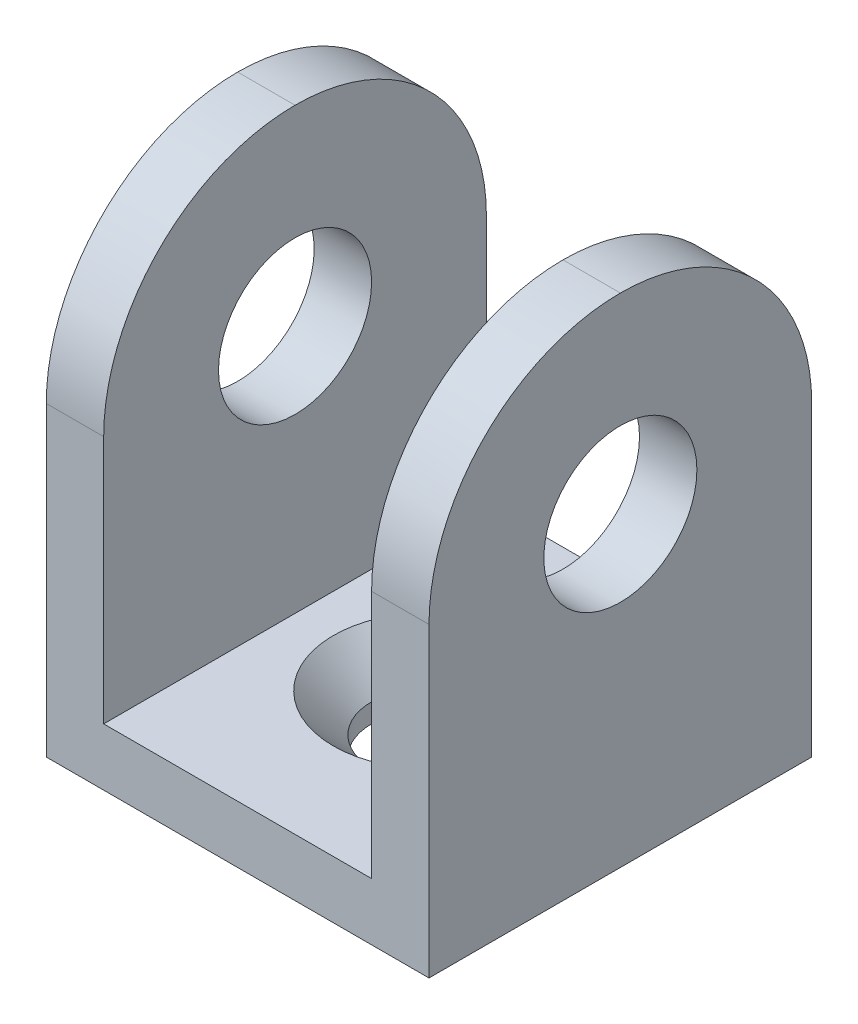
SolidWorks part; units mm, degrees
ref_plane "Alzado" through (0, 0, 0) normal (0, 0, 1) x (1, 0, 0)
ref_plane "Planta" through (0, 0, 0) normal (0, 1, 0) x (1, 0, 0)
ref_plane "Vista lateral" through (0, 0, 0) normal (1, 0, 0) x (0, 0, -1)
sketch "Croquis1" plane through (0, 0, 0) normal (0, 1, 0) x (1, 0, 0)
  line L1 (10, -10) -> (-10, -10)
  line L2 (10, -10) -> (10, 10)
  line L3 (10, 10) -> (-10, 10)
  line L4 (-10, -10) -> (-10, 10)
  line L5 (10, -10) -> (-10, 10) construction
  line L6 (10, 10) -> (-10, -10) construction
  point P0 (0, 0)
  dimension "D1" = 20
extrude "Saliente-Extruir1" add sketch "Croquis1" along normal blind 3
sketch "Croquis2" plane through (0, 3, 0) normal (0, 1, 0) x (1, 0, 0)
  line L0 (-10, -10) -> (10, -10) construction
  line L1 (-10, 10) -> (-7, 10)
  line L2 (-10, 10) -> (-10, -10)
  line L3 (-10, -10) -> (-7, -10)
  line L4 (-7, 10) -> (-7, -10)
  line L6 (10, 10) -> (7, 10)
  line L7 (10, 10) -> (10, -10)
  line L8 (10, -10) -> (7, -10)
  line L9 (7, 10) -> (7, -10)
  dimension "D1" = 3
extrude "Saliente-Extruir2" add sketch "Croquis2" along normal blind 23
fillet "Redondeo1" radius 10 4 edges at (-8.5, 26, -10) (8.5, 26, -10) (8.5, 26, 10) (-8.5, 26, 10)
sketch "Croquis3" plane through (10, 0, 0) normal (1, 0, 0) x (0, 0, -1)
  circle A0 centre (0, 16) radius 4
  dimension "D1" = 8
extrude "Cortar-Extruir1" cut sketch "Croquis3" against normal through all
sketch "Croquis4" plane through (0, 3, 0) normal (0, 1, 0) x (1, 0, 0)
  circle A0 centre (0, 0) radius 3
  dimension "D1" = 6
extrude "Cortar-Extruir2" cut sketch "Croquis4" against normal through all
chamfer "Chaflán1" distance 2 angle 45 1 edges at (0, 3, 3)
